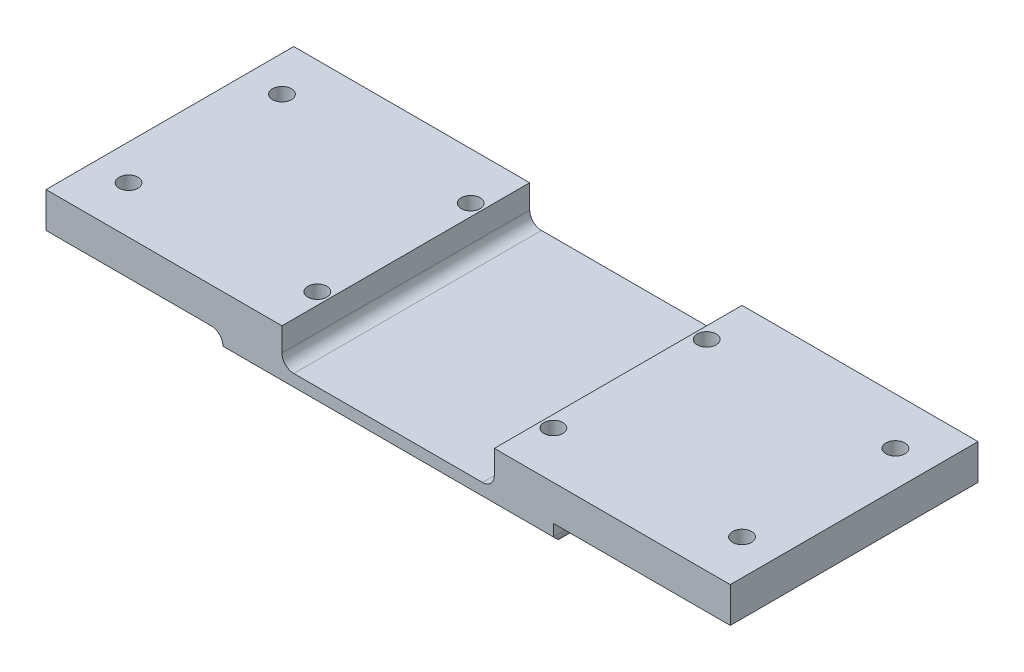
SolidWorks part; units mm, degrees
ref_plane "Front Plane" through (0, 0, 0) normal (0, 0, 1) x (1, 0, 0)
ref_plane "Top Plane" through (0, 0, 0) normal (0, 1, 0) x (1, 0, 0)
ref_plane "Right Plane" through (0, 0, 0) normal (1, 0, 0) x (0, 0, -1)
sketch "Sketch1" plane through (0, 0, 0) normal (0, 1, 0) x (1, 0, 0)
  line L1 (0, 0) -> (184.15, 0)
  line L2 (0, 0) -> (0, 66.675)
  line L3 (0, 66.675) -> (184.15, 66.675)
  line L4 (184.15, 0) -> (184.15, 66.675)
  dimension "D1" = 184.15
  dimension "D2" = 66.675
extrude "Boss-Extrude1" add sketch "Sketch1" along normal blind 9.525
sketch "Sketch4" plane through (0, 0, 0) normal (0, 0, 1) x (1, 0, 0)
  line L0 (0, 0) -> (184.15, 0) construction
  line L1 (47.625, 0) -> (136.525, 0)
  line L2 (47.625, 0) -> (47.625, -6.35)
  line L3 (47.625, -6.35) -> (136.525, -6.35)
  line L4 (136.525, 0) -> (136.525, -6.35)
  line L5 (92.075, 9.525) -> (92.075, -52.0257) construction
  line L6 (0, 9.525) -> (184.15, 9.525) construction
  dimension "D1" = 88.9
  dimension "D2" = 6.35
extrude "Boss-Extrude2" add sketch "Sketch4" against normal up to surface (66.675 mm away) up to face at (92.075, 4.7625, -66.675)
sketch "Sketch5" plane through (0, 9.525, 0) normal (0, 1, 0) x (1, 0, 0)
  line L0 (184.15, 66.675) -> (0, 66.675) construction
  line L1 (120.65, 66.675) -> (63.5, 66.675)
  line L2 (120.65, 66.675) -> (120.65, 0)
  line L3 (120.65, 0) -> (63.5, 0)
  line L4 (63.5, 66.675) -> (63.5, 0)
  line L5 (0, 0) -> (184.15, 0) construction
  line L6 (92.075, 66.675) -> (92.075, -25.2417) construction
  dimension "D1" = 57.15
extrude "Cut-Extrude1" cut sketch "Sketch5" against normal blind 9.525
hole_wizard "#10 Clearance Hole1" positions "Sketch2" profile "Sketch3" hole size "#10" standard "ANSI Inch" end condition up to next
sketch "Sketch2" plane through (0, 9.525, 0) normal (0, 1, 0) x (1, 0, 0)
  line L0 (0, 66.675) -> (0, 0) construction
  line L1 (184.15, 66.675) -> (120.65, 66.675) construction
  line L2 (0, 0) -> (63.5, 0) construction
  line L3 (184.15, 0) -> (184.15, 66.675) construction
  line L4 (184.15, 66.675) -> (136.525, 66.675) construction
  line L7 (136.525, 66.675) -> (47.625, 66.675) construction
  point P0 (9.525, 53.975)
  point P2 (9.525, 12.7)
  point P4 (60.325, 12.7)
  point P6 (60.325, 53.975)
  point P8 (123.825, 53.975)
  point P10 (123.8498, 12.7)
  point P12 (174.625, 12.7)
  point P14 (174.625, 53.975)
  point P27 (0, 0)
  point P32 (132.9083, 79.8454)
  dimension "D1" = 9.525
  dimension "D2" = 12.7
  dimension "D3" = 9.525
  dimension "D4" = 12.7
  dimension "D5" = 12.7
  dimension "D6" = 50.8
  dimension "D7" = 12.7
  dimension "D8" = 50.8
  dimension "D9" = 41.275
  dimension "D10" = 9.525
  dimension "D11" = 12.7
  dimension "D12" = 9.525
  dimension "D13" = 50.8
  dimension "D14" = 41.275
  dimension "D15" = 12.7
sketch "Sketch3" plane through (9.525, 9.525, -53.975) normal (1, 0, 0) x (0, 0, 1)
  line L0 (0, 0) -> (0, 9.525)
  line L1 (0, 9.525) -> (2.5527, 9.525)
  line L2 (2.5527, 9.525) -> (2.5527, 0)
  line L5 (2.5527, 0) -> (0, 0)
  line L11 (0, -6.35) -> (0, 107.95) construction
  dimension "Thru Hole Dia." = 5.1054
  dimension "Thru Hole Depth" = 9.525
fillet "Fillet1" radius 3.175 5 edges at (47.625, 0, -33.3375) (47.625, -6.35, -33.3375) (136.525, -6.35, -33.3375) (63.5, 0, -33.3375) (120.65, 0, -33.3375)
chamfer "Chamfer1" distance 3.175 angle 45 1 edges at (92.075, -6.35, 0) tangent propagation no
ref_plane "Plane1" through (92.075, 0, 0) normal (-1, 0, 0) x (0, 0, 1)
